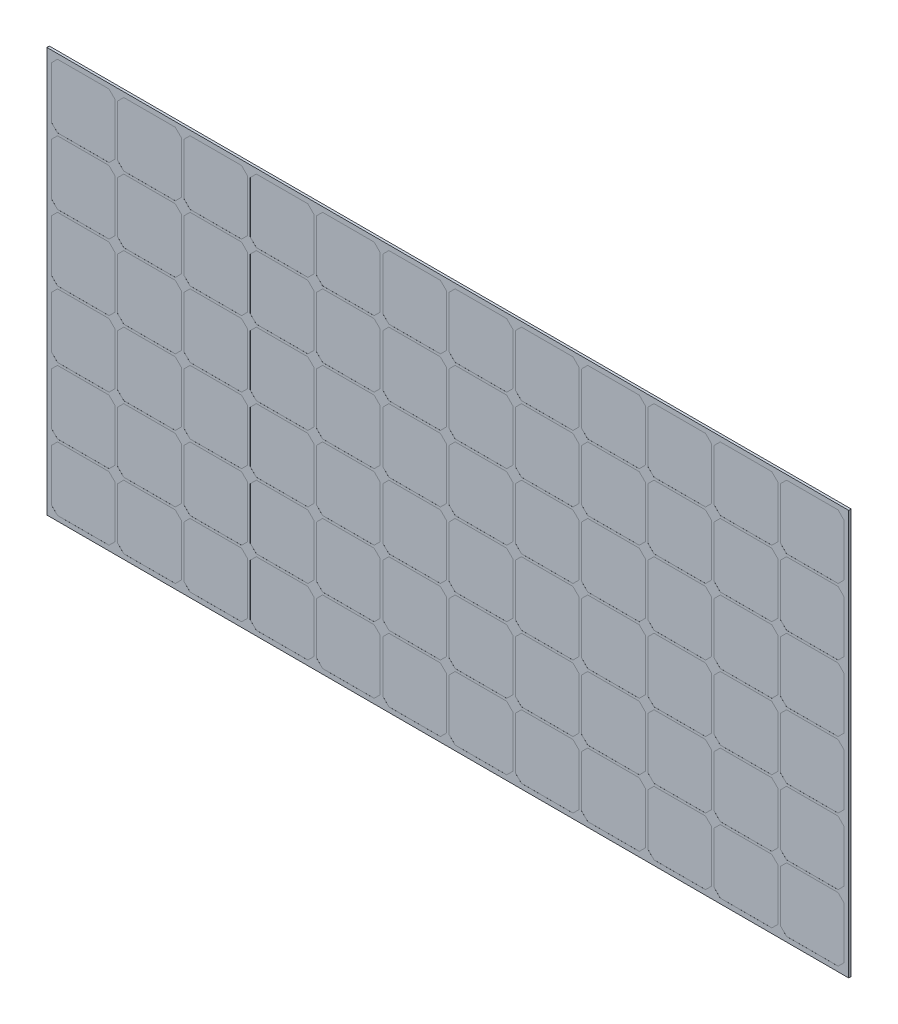
SolidWorks part; units mm, degrees
material "Silicio"
ref_plane "Alzado" through (0, 0, 0) normal (0, 0, 1) x (1, 0, 0)
ref_plane "Planta" through (0, 0, 0) normal (0, 1, 0) x (1, 0, 0)
ref_plane "Vista lateral" through (0, 0, 0) normal (1, 0, 0) x (0, 0, -1)
sketch "Croquis1" plane through (0, 0, 0) normal (0, 0, 1) x (1, 0, 0)
  line L1 (0, 0) -> (1972, 0)
  line L2 (0, 0) -> (0, 996)
  line L3 (0, 996) -> (1972, 996)
  line L4 (1972, 0) -> (1972, 996)
  dimension "D1" = 1972
  dimension "D2" = 996
extrude "Saliente-Extruir1" add sketch "Croquis1" along normal blind 6 contours L3 L4 L1 L2
sketch "Croquis2" plane through (0, 0, 0) normal (0, 0, -1) x (-1, 0, 0)
  line L0 (0, 996) -> (-1972, 996) construction
  line L1 (-1819.125, 983.875) -> (-1945.875, 983.875)
  line L2 (-1804.125, 968.875) -> (-1804.125, 842.125)
  line L3 (-1819.125, 827.125) -> (-1945.875, 827.125)
  line L4 (-1960.875, 968.875) -> (-1960.875, 842.125)
  line L5 (-1972, 0) -> (-1972, 996) construction
  line L6 (-1945.875, 827.125) -> (-1960.875, 842.125)
  line L7 (-1804.125, 842.125) -> (-1819.125, 827.125)
  line L8 (-1804.125, 968.875) -> (-1819.125, 983.875)
  line L9 (-1945.875, 983.875) -> (-1960.875, 968.875)
  line L10 (-1641.125, 968.875) -> (-1641.125, 842.125)
  line L11 (-1641.125, 968.875) -> (-1656.125, 983.875)
  line L12 (-1641.125, 842.125) -> (-1656.125, 827.125)
  line L13 (-1656.125, 983.875) -> (-1782.875, 983.875)
  line L14 (-1782.875, 983.875) -> (-1797.875, 968.875)
  line L15 (-1797.875, 968.875) -> (-1797.875, 842.125)
  line L16 (-1782.875, 827.125) -> (-1797.875, 842.125)
  line L17 (-1656.125, 827.125) -> (-1782.875, 827.125)
  line L18 (-1478.125, 968.875) -> (-1478.125, 842.125)
  line L19 (-1478.125, 968.875) -> (-1493.125, 983.875)
  line L20 (-1478.125, 842.125) -> (-1493.125, 827.125)
  line L21 (-1493.125, 983.875) -> (-1619.875, 983.875)
  line L22 (-1619.875, 983.875) -> (-1634.875, 968.875)
  line L23 (-1634.875, 968.875) -> (-1634.875, 842.125)
  line L24 (-1619.875, 827.125) -> (-1634.875, 842.125)
  line L25 (-1493.125, 827.125) -> (-1619.875, 827.125)
  line L26 (-1315.125, 968.875) -> (-1315.125, 842.125)
  line L27 (-1315.125, 968.875) -> (-1330.125, 983.875)
  line L28 (-1315.125, 842.125) -> (-1330.125, 827.125)
  line L29 (-1330.125, 983.875) -> (-1456.875, 983.875)
  line L30 (-1456.875, 983.875) -> (-1471.875, 968.875)
  line L31 (-1471.875, 968.875) -> (-1471.875, 842.125)
  line L32 (-1456.875, 827.125) -> (-1471.875, 842.125)
  line L33 (-1330.125, 827.125) -> (-1456.875, 827.125)
  line L34 (-1152.125, 968.875) -> (-1152.125, 842.125)
  line L35 (-1152.125, 968.875) -> (-1167.125, 983.875)
  line L36 (-1152.125, 842.125) -> (-1167.125, 827.125)
  line L37 (-1167.125, 983.875) -> (-1293.875, 983.875)
  line L38 (-1293.875, 983.875) -> (-1308.875, 968.875)
  line L39 (-1308.875, 968.875) -> (-1308.875, 842.125)
  line L40 (-1293.875, 827.125) -> (-1308.875, 842.125)
  line L41 (-1167.125, 827.125) -> (-1293.875, 827.125)
  line L42 (-989.125, 968.875) -> (-989.125, 842.125)
  line L43 (-989.125, 968.875) -> (-1004.125, 983.875)
  line L44 (-989.125, 842.125) -> (-1004.125, 827.125)
  line L45 (-1004.125, 983.875) -> (-1130.875, 983.875)
  line L46 (-1130.875, 983.875) -> (-1145.875, 968.875)
  line L47 (-1145.875, 968.875) -> (-1145.875, 842.125)
  line L48 (-1130.875, 827.125) -> (-1145.875, 842.125)
  line L49 (-1004.125, 827.125) -> (-1130.875, 827.125)
  line L50 (-826.125, 968.875) -> (-826.125, 842.125)
  line L51 (-826.125, 968.875) -> (-841.125, 983.875)
  line L52 (-826.125, 842.125) -> (-841.125, 827.125)
  line L53 (-841.125, 983.875) -> (-967.875, 983.875)
  line L54 (-967.875, 983.875) -> (-982.875, 968.875)
  line L55 (-982.875, 968.875) -> (-982.875, 842.125)
  line L56 (-967.875, 827.125) -> (-982.875, 842.125)
  line L57 (-841.125, 827.125) -> (-967.875, 827.125)
  line L58 (-663.125, 968.875) -> (-663.125, 842.125)
  line L59 (-663.125, 968.875) -> (-678.125, 983.875)
  line L60 (-663.125, 842.125) -> (-678.125, 827.125)
  line L61 (-678.125, 983.875) -> (-804.875, 983.875)
  line L62 (-804.875, 983.875) -> (-819.875, 968.875)
  line L63 (-819.875, 968.875) -> (-819.875, 842.125)
  line L64 (-804.875, 827.125) -> (-819.875, 842.125)
  line L65 (-678.125, 827.125) -> (-804.875, 827.125)
  line L66 (-500.125, 968.875) -> (-500.125, 842.125)
  line L67 (-500.125, 968.875) -> (-515.125, 983.875)
  line L68 (-500.125, 842.125) -> (-515.125, 827.125)
  line L69 (-515.125, 983.875) -> (-641.875, 983.875)
  line L70 (-641.875, 983.875) -> (-656.875, 968.875)
  line L71 (-656.875, 968.875) -> (-656.875, 842.125)
  line L72 (-641.875, 827.125) -> (-656.875, 842.125)
  line L73 (-515.125, 827.125) -> (-641.875, 827.125)
  line L74 (-337.125, 968.875) -> (-337.125, 842.125)
  line L75 (-337.125, 968.875) -> (-352.125, 983.875)
  line L76 (-337.125, 842.125) -> (-352.125, 827.125)
  line L77 (-352.125, 983.875) -> (-478.875, 983.875)
  line L78 (-478.875, 983.875) -> (-493.875, 968.875)
  line L79 (-493.875, 968.875) -> (-493.875, 842.125)
  line L80 (-478.875, 827.125) -> (-493.875, 842.125)
  line L81 (-352.125, 827.125) -> (-478.875, 827.125)
  line L82 (-174.125, 968.875) -> (-174.125, 842.125)
  line L83 (-174.125, 968.875) -> (-189.125, 983.875)
  line L84 (-174.125, 842.125) -> (-189.125, 827.125)
  line L85 (-189.125, 983.875) -> (-315.875, 983.875)
  line L86 (-315.875, 983.875) -> (-330.875, 968.875)
  line L87 (-330.875, 968.875) -> (-330.875, 842.125)
  line L88 (-315.875, 827.125) -> (-330.875, 842.125)
  line L89 (-189.125, 827.125) -> (-315.875, 827.125)
  line L90 (-11.125, 968.875) -> (-11.125, 842.125)
  line L91 (-11.125, 968.875) -> (-26.125, 983.875)
  line L92 (-11.125, 842.125) -> (-26.125, 827.125)
  line L93 (-26.125, 983.875) -> (-152.875, 983.875)
  line L94 (-152.875, 983.875) -> (-167.875, 968.875)
  line L95 (-167.875, 968.875) -> (-167.875, 842.125)
  line L96 (-152.875, 827.125) -> (-167.875, 842.125)
  line L97 (-26.125, 827.125) -> (-152.875, 827.125)
  line L98 (-1641.125, 805.875) -> (-1641.125, 679.125)
  line L99 (-1641.125, 805.875) -> (-1656.125, 820.875)
  line L100 (-1641.125, 679.125) -> (-1656.125, 664.125)
  line L101 (-1656.125, 820.875) -> (-1782.875, 820.875)
  line L102 (-1782.875, 820.875) -> (-1797.875, 805.875)
  line L103 (-1797.875, 805.875) -> (-1797.875, 679.125)
  line L104 (-1782.875, 664.125) -> (-1797.875, 679.125)
  line L105 (-1656.125, 664.125) -> (-1782.875, 664.125)
  line L106 (-1478.125, 805.875) -> (-1478.125, 679.125)
  line L107 (-1478.125, 805.875) -> (-1493.125, 820.875)
  line L108 (-1478.125, 679.125) -> (-1493.125, 664.125)
  line L109 (-1493.125, 820.875) -> (-1619.875, 820.875)
  line L110 (-1619.875, 820.875) -> (-1634.875, 805.875)
  line L111 (-1634.875, 805.875) -> (-1634.875, 679.125)
  line L112 (-1619.875, 664.125) -> (-1634.875, 679.125)
  line L113 (-1493.125, 664.125) -> (-1619.875, 664.125)
  line L114 (-1315.125, 805.875) -> (-1315.125, 679.125)
  line L115 (-1315.125, 805.875) -> (-1330.125, 820.875)
  line L116 (-1315.125, 679.125) -> (-1330.125, 664.125)
  line L117 (-1330.125, 820.875) -> (-1456.875, 820.875)
  line L118 (-1456.875, 820.875) -> (-1471.875, 805.875)
  line L119 (-1471.875, 805.875) -> (-1471.875, 679.125)
  line L120 (-1456.875, 664.125) -> (-1471.875, 679.125)
  line L121 (-1330.125, 664.125) -> (-1456.875, 664.125)
  line L122 (-1152.125, 805.875) -> (-1152.125, 679.125)
  line L123 (-1152.125, 805.875) -> (-1167.125, 820.875)
  line L124 (-1152.125, 679.125) -> (-1167.125, 664.125)
  line L125 (-1167.125, 820.875) -> (-1293.875, 820.875)
  line L126 (-1293.875, 820.875) -> (-1308.875, 805.875)
  line L127 (-1308.875, 805.875) -> (-1308.875, 679.125)
  line L128 (-1293.875, 664.125) -> (-1308.875, 679.125)
  line L129 (-1167.125, 664.125) -> (-1293.875, 664.125)
  line L130 (-989.125, 805.875) -> (-989.125, 679.125)
  line L131 (-989.125, 805.875) -> (-1004.125, 820.875)
  line L132 (-989.125, 679.125) -> (-1004.125, 664.125)
  line L133 (-1004.125, 820.875) -> (-1130.875, 820.875)
  line L134 (-1130.875, 820.875) -> (-1145.875, 805.875)
  line L135 (-1145.875, 805.875) -> (-1145.875, 679.125)
  line L136 (-1130.875, 664.125) -> (-1145.875, 679.125)
  line L137 (-1004.125, 664.125) -> (-1130.875, 664.125)
  line L138 (-826.125, 805.875) -> (-826.125, 679.125)
  line L139 (-826.125, 805.875) -> (-841.125, 820.875)
  line L140 (-826.125, 679.125) -> (-841.125, 664.125)
  line L141 (-841.125, 820.875) -> (-967.875, 820.875)
  line L142 (-967.875, 820.875) -> (-982.875, 805.875)
  line L143 (-982.875, 805.875) -> (-982.875, 679.125)
  line L144 (-967.875, 664.125) -> (-982.875, 679.125)
  line L145 (-841.125, 664.125) -> (-967.875, 664.125)
  line L146 (-663.125, 805.875) -> (-663.125, 679.125)
  line L147 (-663.125, 805.875) -> (-678.125, 820.875)
  line L148 (-663.125, 679.125) -> (-678.125, 664.125)
  line L149 (-678.125, 820.875) -> (-804.875, 820.875)
  line L150 (-804.875, 820.875) -> (-819.875, 805.875)
  line L151 (-819.875, 805.875) -> (-819.875, 679.125)
  line L152 (-804.875, 664.125) -> (-819.875, 679.125)
  line L153 (-678.125, 664.125) -> (-804.875, 664.125)
  line L154 (-500.125, 805.875) -> (-500.125, 679.125)
  line L155 (-500.125, 805.875) -> (-515.125, 820.875)
  line L156 (-500.125, 679.125) -> (-515.125, 664.125)
  line L157 (-515.125, 820.875) -> (-641.875, 820.875)
  line L158 (-641.875, 820.875) -> (-656.875, 805.875)
  line L159 (-656.875, 805.875) -> (-656.875, 679.125)
  line L160 (-641.875, 664.125) -> (-656.875, 679.125)
  line L161 (-515.125, 664.125) -> (-641.875, 664.125)
  line L162 (-337.125, 805.875) -> (-337.125, 679.125)
  line L163 (-337.125, 805.875) -> (-352.125, 820.875)
  line L164 (-337.125, 679.125) -> (-352.125, 664.125)
  line L165 (-352.125, 820.875) -> (-478.875, 820.875)
  line L166 (-478.875, 820.875) -> (-493.875, 805.875)
  line L167 (-493.875, 805.875) -> (-493.875, 679.125)
  line L168 (-478.875, 664.125) -> (-493.875, 679.125)
  line L169 (-352.125, 664.125) -> (-478.875, 664.125)
  line L170 (-174.125, 805.875) -> (-174.125, 679.125)
  line L171 (-174.125, 805.875) -> (-189.125, 820.875)
  line L172 (-174.125, 679.125) -> (-189.125, 664.125)
  line L173 (-189.125, 820.875) -> (-315.875, 820.875)
  line L174 (-315.875, 820.875) -> (-330.875, 805.875)
  line L175 (-330.875, 805.875) -> (-330.875, 679.125)
  line L176 (-315.875, 664.125) -> (-330.875, 679.125)
  line L177 (-189.125, 664.125) -> (-315.875, 664.125)
  line L178 (-11.125, 805.875) -> (-11.125, 679.125)
  line L179 (-11.125, 805.875) -> (-26.125, 820.875)
  line L180 (-11.125, 679.125) -> (-26.125, 664.125)
  line L181 (-26.125, 820.875) -> (-152.875, 820.875)
  line L182 (-152.875, 820.875) -> (-167.875, 805.875)
  line L183 (-167.875, 805.875) -> (-167.875, 679.125)
  line L184 (-152.875, 664.125) -> (-167.875, 679.125)
  line L185 (-26.125, 664.125) -> (-152.875, 664.125)
  line L186 (-1641.125, 642.875) -> (-1641.125, 516.125)
  line L187 (-1641.125, 642.875) -> (-1656.125, 657.875)
  line L188 (-1641.125, 516.125) -> (-1656.125, 501.125)
  line L189 (-1656.125, 657.875) -> (-1782.875, 657.875)
  line L190 (-1782.875, 657.875) -> (-1797.875, 642.875)
  line L191 (-1797.875, 642.875) -> (-1797.875, 516.125)
  line L192 (-1782.875, 501.125) -> (-1797.875, 516.125)
  line L193 (-1656.125, 501.125) -> (-1782.875, 501.125)
  line L194 (-1478.125, 642.875) -> (-1478.125, 516.125)
  line L195 (-1478.125, 642.875) -> (-1493.125, 657.875)
  line L196 (-1478.125, 516.125) -> (-1493.125, 501.125)
  line L197 (-1493.125, 657.875) -> (-1619.875, 657.875)
  line L198 (-1619.875, 657.875) -> (-1634.875, 642.875)
  line L199 (-1634.875, 642.875) -> (-1634.875, 516.125)
  line L200 (-1619.875, 501.125) -> (-1634.875, 516.125)
  line L201 (-1493.125, 501.125) -> (-1619.875, 501.125)
  line L202 (-1315.125, 642.875) -> (-1315.125, 516.125)
  line L203 (-1315.125, 642.875) -> (-1330.125, 657.875)
  line L204 (-1315.125, 516.125) -> (-1330.125, 501.125)
  line L205 (-1330.125, 657.875) -> (-1456.875, 657.875)
  line L206 (-1456.875, 657.875) -> (-1471.875, 642.875)
  line L207 (-1471.875, 642.875) -> (-1471.875, 516.125)
  line L208 (-1456.875, 501.125) -> (-1471.875, 516.125)
  line L209 (-1330.125, 501.125) -> (-1456.875, 501.125)
  line L210 (-1152.125, 642.875) -> (-1152.125, 516.125)
  line L211 (-1152.125, 642.875) -> (-1167.125, 657.875)
  line L212 (-1152.125, 516.125) -> (-1167.125, 501.125)
  line L213 (-1167.125, 657.875) -> (-1293.875, 657.875)
  line L214 (-1293.875, 657.875) -> (-1308.875, 642.875)
  line L215 (-1308.875, 642.875) -> (-1308.875, 516.125)
  line L216 (-1293.875, 501.125) -> (-1308.875, 516.125)
  line L217 (-1167.125, 501.125) -> (-1293.875, 501.125)
  line L218 (-989.125, 642.875) -> (-989.125, 516.125)
  line L219 (-989.125, 642.875) -> (-1004.125, 657.875)
  line L220 (-989.125, 516.125) -> (-1004.125, 501.125)
  line L221 (-1004.125, 657.875) -> (-1130.875, 657.875)
  line L222 (-1130.875, 657.875) -> (-1145.875, 642.875)
  line L223 (-1145.875, 642.875) -> (-1145.875, 516.125)
  line L224 (-1130.875, 501.125) -> (-1145.875, 516.125)
  line L225 (-1004.125, 501.125) -> (-1130.875, 501.125)
  line L226 (-826.125, 642.875) -> (-826.125, 516.125)
  line L227 (-826.125, 642.875) -> (-841.125, 657.875)
  line L228 (-826.125, 516.125) -> (-841.125, 501.125)
  line L229 (-841.125, 657.875) -> (-967.875, 657.875)
  line L230 (-967.875, 657.875) -> (-982.875, 642.875)
  line L231 (-982.875, 642.875) -> (-982.875, 516.125)
  line L232 (-967.875, 501.125) -> (-982.875, 516.125)
  line L233 (-841.125, 501.125) -> (-967.875, 501.125)
  line L234 (-663.125, 642.875) -> (-663.125, 516.125)
  line L235 (-663.125, 642.875) -> (-678.125, 657.875)
  line L236 (-663.125, 516.125) -> (-678.125, 501.125)
  line L237 (-678.125, 657.875) -> (-804.875, 657.875)
  line L238 (-804.875, 657.875) -> (-819.875, 642.875)
  line L239 (-819.875, 642.875) -> (-819.875, 516.125)
  line L240 (-804.875, 501.125) -> (-819.875, 516.125)
  line L241 (-678.125, 501.125) -> (-804.875, 501.125)
  line L242 (-500.125, 642.875) -> (-500.125, 516.125)
  line L243 (-500.125, 642.875) -> (-515.125, 657.875)
  line L244 (-500.125, 516.125) -> (-515.125, 501.125)
  line L245 (-515.125, 657.875) -> (-641.875, 657.875)
  line L246 (-641.875, 657.875) -> (-656.875, 642.875)
  line L247 (-656.875, 642.875) -> (-656.875, 516.125)
  line L248 (-641.875, 501.125) -> (-656.875, 516.125)
  line L249 (-515.125, 501.125) -> (-641.875, 501.125)
  line L250 (-337.125, 642.875) -> (-337.125, 516.125)
  line L251 (-337.125, 642.875) -> (-352.125, 657.875)
  line L252 (-337.125, 516.125) -> (-352.125, 501.125)
  line L253 (-352.125, 657.875) -> (-478.875, 657.875)
  line L254 (-478.875, 657.875) -> (-493.875, 642.875)
  line L255 (-493.875, 642.875) -> (-493.875, 516.125)
  line L256 (-478.875, 501.125) -> (-493.875, 516.125)
  line L257 (-352.125, 501.125) -> (-478.875, 501.125)
  line L258 (-174.125, 642.875) -> (-174.125, 516.125)
  line L259 (-174.125, 642.875) -> (-189.125, 657.875)
  line L260 (-174.125, 516.125) -> (-189.125, 501.125)
  line L261 (-189.125, 657.875) -> (-315.875, 657.875)
  line L262 (-315.875, 657.875) -> (-330.875, 642.875)
  line L263 (-330.875, 642.875) -> (-330.875, 516.125)
  line L264 (-315.875, 501.125) -> (-330.875, 516.125)
  line L265 (-189.125, 501.125) -> (-315.875, 501.125)
  line L266 (-11.125, 642.875) -> (-11.125, 516.125)
  line L267 (-11.125, 642.875) -> (-26.125, 657.875)
  line L268 (-11.125, 516.125) -> (-26.125, 501.125)
  line L269 (-26.125, 657.875) -> (-152.875, 657.875)
  line L270 (-152.875, 657.875) -> (-167.875, 642.875)
  line L271 (-167.875, 642.875) -> (-167.875, 516.125)
  line L272 (-152.875, 501.125) -> (-167.875, 516.125)
  line L273 (-26.125, 501.125) -> (-152.875, 501.125)
  line L274 (-1641.125, 479.875) -> (-1641.125, 353.125)
  line L275 (-1641.125, 479.875) -> (-1656.125, 494.875)
  line L276 (-1641.125, 353.125) -> (-1656.125, 338.125)
  line L277 (-1656.125, 494.875) -> (-1782.875, 494.875)
  line L278 (-1782.875, 494.875) -> (-1797.875, 479.875)
  line L279 (-1797.875, 479.875) -> (-1797.875, 353.125)
  line L280 (-1782.875, 338.125) -> (-1797.875, 353.125)
  line L281 (-1656.125, 338.125) -> (-1782.875, 338.125)
  line L282 (-1478.125, 479.875) -> (-1478.125, 353.125)
  line L283 (-1478.125, 479.875) -> (-1493.125, 494.875)
  line L284 (-1478.125, 353.125) -> (-1493.125, 338.125)
  line L285 (-1493.125, 494.875) -> (-1619.875, 494.875)
  line L286 (-1619.875, 494.875) -> (-1634.875, 479.875)
  line L287 (-1634.875, 479.875) -> (-1634.875, 353.125)
  line L288 (-1619.875, 338.125) -> (-1634.875, 353.125)
  line L289 (-1493.125, 338.125) -> (-1619.875, 338.125)
  line L290 (-1315.125, 479.875) -> (-1315.125, 353.125)
  line L291 (-1315.125, 479.875) -> (-1330.125, 494.875)
  line L292 (-1315.125, 353.125) -> (-1330.125, 338.125)
  line L293 (-1330.125, 494.875) -> (-1456.875, 494.875)
  line L294 (-1456.875, 494.875) -> (-1471.875, 479.875)
  line L295 (-1471.875, 479.875) -> (-1471.875, 353.125)
  line L296 (-1456.875, 338.125) -> (-1471.875, 353.125)
  line L297 (-1330.125, 338.125) -> (-1456.875, 338.125)
  line L298 (-1152.125, 479.875) -> (-1152.125, 353.125)
  line L299 (-1152.125, 479.875) -> (-1167.125, 494.875)
  line L300 (-1152.125, 353.125) -> (-1167.125, 338.125)
  line L301 (-1167.125, 494.875) -> (-1293.875, 494.875)
  line L302 (-1293.875, 494.875) -> (-1308.875, 479.875)
  line L303 (-1308.875, 479.875) -> (-1308.875, 353.125)
  line L304 (-1293.875, 338.125) -> (-1308.875, 353.125)
  line L305 (-1167.125, 338.125) -> (-1293.875, 338.125)
  line L306 (-989.125, 479.875) -> (-989.125, 353.125)
  line L307 (-989.125, 479.875) -> (-1004.125, 494.875)
  line L308 (-989.125, 353.125) -> (-1004.125, 338.125)
  line L309 (-1004.125, 494.875) -> (-1130.875, 494.875)
  line L310 (-1130.875, 494.875) -> (-1145.875, 479.875)
  line L311 (-1145.875, 479.875) -> (-1145.875, 353.125)
  line L312 (-1130.875, 338.125) -> (-1145.875, 353.125)
  line L313 (-1004.125, 338.125) -> (-1130.875, 338.125)
  line L314 (-826.125, 479.875) -> (-826.125, 353.125)
  line L315 (-826.125, 479.875) -> (-841.125, 494.875)
  line L316 (-826.125, 353.125) -> (-841.125, 338.125)
  line L317 (-841.125, 494.875) -> (-967.875, 494.875)
  line L318 (-967.875, 494.875) -> (-982.875, 479.875)
  line L319 (-982.875, 479.875) -> (-982.875, 353.125)
  line L320 (-967.875, 338.125) -> (-982.875, 353.125)
  line L321 (-841.125, 338.125) -> (-967.875, 338.125)
  line L322 (-663.125, 479.875) -> (-663.125, 353.125)
  line L323 (-663.125, 479.875) -> (-678.125, 494.875)
  line L324 (-663.125, 353.125) -> (-678.125, 338.125)
  line L325 (-678.125, 494.875) -> (-804.875, 494.875)
  line L326 (-804.875, 494.875) -> (-819.875, 479.875)
  line L327 (-819.875, 479.875) -> (-819.875, 353.125)
  line L328 (-804.875, 338.125) -> (-819.875, 353.125)
  line L329 (-678.125, 338.125) -> (-804.875, 338.125)
  line L330 (-500.125, 479.875) -> (-500.125, 353.125)
  line L331 (-500.125, 479.875) -> (-515.125, 494.875)
  line L332 (-500.125, 353.125) -> (-515.125, 338.125)
  line L333 (-515.125, 494.875) -> (-641.875, 494.875)
  line L334 (-641.875, 494.875) -> (-656.875, 479.875)
  line L335 (-656.875, 479.875) -> (-656.875, 353.125)
  line L336 (-641.875, 338.125) -> (-656.875, 353.125)
  line L337 (-515.125, 338.125) -> (-641.875, 338.125)
  line L338 (-337.125, 479.875) -> (-337.125, 353.125)
  line L339 (-337.125, 479.875) -> (-352.125, 494.875)
  line L340 (-337.125, 353.125) -> (-352.125, 338.125)
  line L341 (-352.125, 494.875) -> (-478.875, 494.875)
  line L342 (-478.875, 494.875) -> (-493.875, 479.875)
  line L343 (-493.875, 479.875) -> (-493.875, 353.125)
  line L344 (-478.875, 338.125) -> (-493.875, 353.125)
  line L345 (-352.125, 338.125) -> (-478.875, 338.125)
  line L346 (-174.125, 479.875) -> (-174.125, 353.125)
  line L347 (-174.125, 479.875) -> (-189.125, 494.875)
  line L348 (-174.125, 353.125) -> (-189.125, 338.125)
  line L349 (-189.125, 494.875) -> (-315.875, 494.875)
  line L350 (-315.875, 494.875) -> (-330.875, 479.875)
  line L351 (-330.875, 479.875) -> (-330.875, 353.125)
  line L352 (-315.875, 338.125) -> (-330.875, 353.125)
  line L353 (-189.125, 338.125) -> (-315.875, 338.125)
  line L354 (-11.125, 479.875) -> (-11.125, 353.125)
  line L355 (-11.125, 479.875) -> (-26.125, 494.875)
  line L356 (-11.125, 353.125) -> (-26.125, 338.125)
  line L357 (-26.125, 494.875) -> (-152.875, 494.875)
  line L358 (-152.875, 494.875) -> (-167.875, 479.875)
  line L359 (-167.875, 479.875) -> (-167.875, 353.125)
  line L360 (-152.875, 338.125) -> (-167.875, 353.125)
  line L361 (-26.125, 338.125) -> (-152.875, 338.125)
  line L362 (-1641.125, 316.875) -> (-1641.125, 190.125)
  line L363 (-1641.125, 316.875) -> (-1656.125, 331.875)
  line L364 (-1641.125, 190.125) -> (-1656.125, 175.125)
  line L365 (-1656.125, 331.875) -> (-1782.875, 331.875)
  line L366 (-1782.875, 331.875) -> (-1797.875, 316.875)
  line L367 (-1797.875, 316.875) -> (-1797.875, 190.125)
  line L368 (-1782.875, 175.125) -> (-1797.875, 190.125)
  line L369 (-1656.125, 175.125) -> (-1782.875, 175.125)
  line L370 (-1478.125, 316.875) -> (-1478.125, 190.125)
  line L371 (-1478.125, 316.875) -> (-1493.125, 331.875)
  line L372 (-1478.125, 190.125) -> (-1493.125, 175.125)
  line L373 (-1493.125, 331.875) -> (-1619.875, 331.875)
  line L374 (-1619.875, 331.875) -> (-1634.875, 316.875)
  line L375 (-1634.875, 316.875) -> (-1634.875, 190.125)
  line L376 (-1619.875, 175.125) -> (-1634.875, 190.125)
  line L377 (-1493.125, 175.125) -> (-1619.875, 175.125)
  line L378 (-1315.125, 316.875) -> (-1315.125, 190.125)
  line L379 (-1315.125, 316.875) -> (-1330.125, 331.875)
  line L380 (-1315.125, 190.125) -> (-1330.125, 175.125)
  line L381 (-1330.125, 331.875) -> (-1456.875, 331.875)
  line L382 (-1456.875, 331.875) -> (-1471.875, 316.875)
  line L383 (-1471.875, 316.875) -> (-1471.875, 190.125)
  line L384 (-1456.875, 175.125) -> (-1471.875, 190.125)
  line L385 (-1330.125, 175.125) -> (-1456.875, 175.125)
  line L386 (-1152.125, 316.875) -> (-1152.125, 190.125)
  line L387 (-1152.125, 316.875) -> (-1167.125, 331.875)
  line L388 (-1152.125, 190.125) -> (-1167.125, 175.125)
  line L389 (-1167.125, 331.875) -> (-1293.875, 331.875)
  line L390 (-1293.875, 331.875) -> (-1308.875, 316.875)
  line L391 (-1308.875, 316.875) -> (-1308.875, 190.125)
  line L392 (-1293.875, 175.125) -> (-1308.875, 190.125)
  line L393 (-1167.125, 175.125) -> (-1293.875, 175.125)
  line L394 (-989.125, 316.875) -> (-989.125, 190.125)
  line L395 (-989.125, 316.875) -> (-1004.125, 331.875)
  line L396 (-989.125, 190.125) -> (-1004.125, 175.125)
  line L397 (-1004.125, 331.875) -> (-1130.875, 331.875)
  line L398 (-1130.875, 331.875) -> (-1145.875, 316.875)
  line L399 (-1145.875, 316.875) -> (-1145.875, 190.125)
  line L400 (-1130.875, 175.125) -> (-1145.875, 190.125)
  line L401 (-1004.125, 175.125) -> (-1130.875, 175.125)
  line L402 (-826.125, 316.875) -> (-826.125, 190.125)
  line L403 (-826.125, 316.875) -> (-841.125, 331.875)
  line L404 (-826.125, 190.125) -> (-841.125, 175.125)
  line L405 (-841.125, 331.875) -> (-967.875, 331.875)
  line L406 (-967.875, 331.875) -> (-982.875, 316.875)
  line L407 (-982.875, 316.875) -> (-982.875, 190.125)
  line L408 (-967.875, 175.125) -> (-982.875, 190.125)
  line L409 (-841.125, 175.125) -> (-967.875, 175.125)
  line L410 (-663.125, 316.875) -> (-663.125, 190.125)
  line L411 (-663.125, 316.875) -> (-678.125, 331.875)
  line L412 (-663.125, 190.125) -> (-678.125, 175.125)
  line L413 (-678.125, 331.875) -> (-804.875, 331.875)
  line L414 (-804.875, 331.875) -> (-819.875, 316.875)
  line L415 (-819.875, 316.875) -> (-819.875, 190.125)
  line L416 (-804.875, 175.125) -> (-819.875, 190.125)
  line L417 (-678.125, 175.125) -> (-804.875, 175.125)
  line L418 (-500.125, 316.875) -> (-500.125, 190.125)
  line L419 (-500.125, 316.875) -> (-515.125, 331.875)
  line L420 (-500.125, 190.125) -> (-515.125, 175.125)
  line L421 (-515.125, 331.875) -> (-641.875, 331.875)
  line L422 (-641.875, 331.875) -> (-656.875, 316.875)
  line L423 (-656.875, 316.875) -> (-656.875, 190.125)
  line L424 (-641.875, 175.125) -> (-656.875, 190.125)
  line L425 (-515.125, 175.125) -> (-641.875, 175.125)
  line L426 (-337.125, 316.875) -> (-337.125, 190.125)
  line L427 (-337.125, 316.875) -> (-352.125, 331.875)
  line L428 (-337.125, 190.125) -> (-352.125, 175.125)
  line L429 (-352.125, 331.875) -> (-478.875, 331.875)
  line L430 (-478.875, 331.875) -> (-493.875, 316.875)
  line L431 (-493.875, 316.875) -> (-493.875, 190.125)
  line L432 (-478.875, 175.125) -> (-493.875, 190.125)
  line L433 (-352.125, 175.125) -> (-478.875, 175.125)
  line L434 (-174.125, 316.875) -> (-174.125, 190.125)
  line L435 (-174.125, 316.875) -> (-189.125, 331.875)
  line L436 (-174.125, 190.125) -> (-189.125, 175.125)
  line L437 (-189.125, 331.875) -> (-315.875, 331.875)
  line L438 (-315.875, 331.875) -> (-330.875, 316.875)
  line L439 (-330.875, 316.875) -> (-330.875, 190.125)
  line L440 (-315.875, 175.125) -> (-330.875, 190.125)
  line L441 (-189.125, 175.125) -> (-315.875, 175.125)
  line L442 (-11.125, 316.875) -> (-11.125, 190.125)
  line L443 (-11.125, 316.875) -> (-26.125, 331.875)
  line L444 (-11.125, 190.125) -> (-26.125, 175.125)
  line L445 (-26.125, 331.875) -> (-152.875, 331.875)
  line L446 (-152.875, 331.875) -> (-167.875, 316.875)
  line L447 (-167.875, 316.875) -> (-167.875, 190.125)
  line L448 (-152.875, 175.125) -> (-167.875, 190.125)
  line L449 (-26.125, 175.125) -> (-152.875, 175.125)
  line L450 (-1641.125, 153.875) -> (-1641.125, 27.125)
  line L451 (-1641.125, 153.875) -> (-1656.125, 168.875)
  line L452 (-1641.125, 27.125) -> (-1656.125, 12.125)
  line L453 (-1656.125, 168.875) -> (-1782.875, 168.875)
  line L454 (-1782.875, 168.875) -> (-1797.875, 153.875)
  line L455 (-1797.875, 153.875) -> (-1797.875, 27.125)
  line L456 (-1782.875, 12.125) -> (-1797.875, 27.125)
  line L457 (-1656.125, 12.125) -> (-1782.875, 12.125)
  line L458 (-1478.125, 153.875) -> (-1478.125, 27.125)
  line L459 (-1478.125, 153.875) -> (-1493.125, 168.875)
  line L460 (-1478.125, 27.125) -> (-1493.125, 12.125)
  line L461 (-1493.125, 168.875) -> (-1619.875, 168.875)
  line L462 (-1619.875, 168.875) -> (-1634.875, 153.875)
  line L463 (-1634.875, 153.875) -> (-1634.875, 27.125)
  line L464 (-1619.875, 12.125) -> (-1634.875, 27.125)
  line L465 (-1493.125, 12.125) -> (-1619.875, 12.125)
  line L466 (-1315.125, 153.875) -> (-1315.125, 27.125)
  line L467 (-1315.125, 153.875) -> (-1330.125, 168.875)
  line L468 (-1315.125, 27.125) -> (-1330.125, 12.125)
  line L469 (-1330.125, 168.875) -> (-1456.875, 168.875)
  line L470 (-1456.875, 168.875) -> (-1471.875, 153.875)
  line L471 (-1471.875, 153.875) -> (-1471.875, 27.125)
  line L472 (-1456.875, 12.125) -> (-1471.875, 27.125)
  line L473 (-1330.125, 12.125) -> (-1456.875, 12.125)
  line L474 (-1152.125, 153.875) -> (-1152.125, 27.125)
  line L475 (-1152.125, 153.875) -> (-1167.125, 168.875)
  line L476 (-1152.125, 27.125) -> (-1167.125, 12.125)
  line L477 (-1167.125, 168.875) -> (-1293.875, 168.875)
  line L478 (-1293.875, 168.875) -> (-1308.875, 153.875)
  line L479 (-1308.875, 153.875) -> (-1308.875, 27.125)
  line L480 (-1293.875, 12.125) -> (-1308.875, 27.125)
  line L481 (-1167.125, 12.125) -> (-1293.875, 12.125)
  line L482 (-989.125, 153.875) -> (-989.125, 27.125)
  line L483 (-989.125, 153.875) -> (-1004.125, 168.875)
  line L484 (-989.125, 27.125) -> (-1004.125, 12.125)
  line L485 (-1004.125, 168.875) -> (-1130.875, 168.875)
  line L486 (-1130.875, 168.875) -> (-1145.875, 153.875)
  line L487 (-1145.875, 153.875) -> (-1145.875, 27.125)
  line L488 (-1130.875, 12.125) -> (-1145.875, 27.125)
  line L489 (-1004.125, 12.125) -> (-1130.875, 12.125)
  line L490 (-826.125, 153.875) -> (-826.125, 27.125)
  line L491 (-826.125, 153.875) -> (-841.125, 168.875)
  line L492 (-826.125, 27.125) -> (-841.125, 12.125)
  line L493 (-841.125, 168.875) -> (-967.875, 168.875)
  line L494 (-967.875, 168.875) -> (-982.875, 153.875)
  line L495 (-982.875, 153.875) -> (-982.875, 27.125)
  line L496 (-967.875, 12.125) -> (-982.875, 27.125)
  line L497 (-841.125, 12.125) -> (-967.875, 12.125)
  line L498 (-663.125, 153.875) -> (-663.125, 27.125)
  line L499 (-663.125, 153.875) -> (-678.125, 168.875)
  line L500 (-663.125, 27.125) -> (-678.125, 12.125)
  line L501 (-678.125, 168.875) -> (-804.875, 168.875)
  line L502 (-804.875, 168.875) -> (-819.875, 153.875)
  line L503 (-819.875, 153.875) -> (-819.875, 27.125)
  line L504 (-804.875, 12.125) -> (-819.875, 27.125)
  line L505 (-678.125, 12.125) -> (-804.875, 12.125)
  line L506 (-500.125, 153.875) -> (-500.125, 27.125)
  line L507 (-500.125, 153.875) -> (-515.125, 168.875)
  line L508 (-500.125, 27.125) -> (-515.125, 12.125)
  line L509 (-515.125, 168.875) -> (-641.875, 168.875)
  line L510 (-641.875, 168.875) -> (-656.875, 153.875)
  line L511 (-656.875, 153.875) -> (-656.875, 27.125)
  line L512 (-641.875, 12.125) -> (-656.875, 27.125)
  line L513 (-515.125, 12.125) -> (-641.875, 12.125)
  line L514 (-337.125, 153.875) -> (-337.125, 27.125)
  line L515 (-337.125, 153.875) -> (-352.125, 168.875)
  line L516 (-337.125, 27.125) -> (-352.125, 12.125)
  line L517 (-352.125, 168.875) -> (-478.875, 168.875)
  line L518 (-478.875, 168.875) -> (-493.875, 153.875)
  line L519 (-493.875, 153.875) -> (-493.875, 27.125)
  line L520 (-478.875, 12.125) -> (-493.875, 27.125)
  line L521 (-352.125, 12.125) -> (-478.875, 12.125)
  line L522 (-174.125, 153.875) -> (-174.125, 27.125)
  line L523 (-174.125, 153.875) -> (-189.125, 168.875)
  line L524 (-174.125, 27.125) -> (-189.125, 12.125)
  line L525 (-189.125, 168.875) -> (-315.875, 168.875)
  line L526 (-315.875, 168.875) -> (-330.875, 153.875)
  line L527 (-330.875, 153.875) -> (-330.875, 27.125)
  line L528 (-315.875, 12.125) -> (-330.875, 27.125)
  line L529 (-189.125, 12.125) -> (-315.875, 12.125)
  line L530 (-11.125, 153.875) -> (-11.125, 27.125)
  line L531 (-11.125, 153.875) -> (-26.125, 168.875)
  line L532 (-11.125, 27.125) -> (-26.125, 12.125)
  line L533 (-26.125, 168.875) -> (-152.875, 168.875)
  line L534 (-152.875, 168.875) -> (-167.875, 153.875)
  line L535 (-167.875, 153.875) -> (-167.875, 27.125)
  line L536 (-152.875, 12.125) -> (-167.875, 27.125)
  line L537 (-26.125, 12.125) -> (-152.875, 12.125)
  line L538 (-1804.125, 805.875) -> (-1804.125, 679.125)
  line L539 (-1804.125, 805.875) -> (-1819.125, 820.875)
  line L540 (-1804.125, 679.125) -> (-1819.125, 664.125)
  line L541 (-1819.125, 820.875) -> (-1945.875, 820.875)
  line L542 (-1945.875, 820.875) -> (-1960.875, 805.875)
  line L543 (-1960.875, 805.875) -> (-1960.875, 679.125)
  line L544 (-1945.875, 664.125) -> (-1960.875, 679.125)
  line L545 (-1819.125, 664.125) -> (-1945.875, 664.125)
  line L546 (-1804.125, 642.875) -> (-1804.125, 516.125)
  line L547 (-1804.125, 642.875) -> (-1819.125, 657.875)
  line L548 (-1804.125, 516.125) -> (-1819.125, 501.125)
  line L549 (-1819.125, 657.875) -> (-1945.875, 657.875)
  line L550 (-1945.875, 657.875) -> (-1960.875, 642.875)
  line L551 (-1960.875, 642.875) -> (-1960.875, 516.125)
  line L552 (-1945.875, 501.125) -> (-1960.875, 516.125)
  line L553 (-1819.125, 501.125) -> (-1945.875, 501.125)
  line L554 (-1804.125, 479.875) -> (-1804.125, 353.125)
  line L555 (-1804.125, 479.875) -> (-1819.125, 494.875)
  line L556 (-1804.125, 353.125) -> (-1819.125, 338.125)
  line L557 (-1819.125, 494.875) -> (-1945.875, 494.875)
  line L558 (-1945.875, 494.875) -> (-1960.875, 479.875)
  line L559 (-1960.875, 479.875) -> (-1960.875, 353.125)
  line L560 (-1945.875, 338.125) -> (-1960.875, 353.125)
  line L561 (-1819.125, 338.125) -> (-1945.875, 338.125)
  line L562 (-1804.125, 316.875) -> (-1804.125, 190.125)
  line L563 (-1804.125, 316.875) -> (-1819.125, 331.875)
  line L564 (-1804.125, 190.125) -> (-1819.125, 175.125)
  line L565 (-1819.125, 331.875) -> (-1945.875, 331.875)
  line L566 (-1945.875, 331.875) -> (-1960.875, 316.875)
  line L567 (-1960.875, 316.875) -> (-1960.875, 190.125)
  line L568 (-1945.875, 175.125) -> (-1960.875, 190.125)
  line L569 (-1819.125, 175.125) -> (-1945.875, 175.125)
  line L570 (-1804.125, 153.875) -> (-1804.125, 27.125)
  line L571 (-1804.125, 153.875) -> (-1819.125, 168.875)
  line L572 (-1804.125, 27.125) -> (-1819.125, 12.125)
  line L573 (-1819.125, 168.875) -> (-1945.875, 168.875)
  line L574 (-1945.875, 168.875) -> (-1960.875, 153.875)
  line L575 (-1960.875, 153.875) -> (-1960.875, 27.125)
  line L576 (-1945.875, 12.125) -> (-1960.875, 27.125)
  line L577 (-1819.125, 12.125) -> (-1945.875, 12.125)
  point P0 (-1804.125, 983.875)
  point P1 (-1960.875, 827.125)
  point P2 (-1804.125, 827.125)
  point P3 (-1960.875, 983.875)
  dimension "D1" = 156.75
  dimension "D2" = 156.75
  dimension "D3" = 12.125
  dimension "D4" = 11.125
  dimension "D5" = 12
  dimension "D6" = 6
extrude "Cortar-Extruir1" cut sketch "Croquis2" against normal blind 0.1
ref_plane "Plano1" through (0, 0, 3) normal (0, 0, -1) x (-1, 0, 0)
mirror "Simetría1" about plane through (0, 0, 3) normal (0, 0, -1) of "Cortar-Extruir1"
